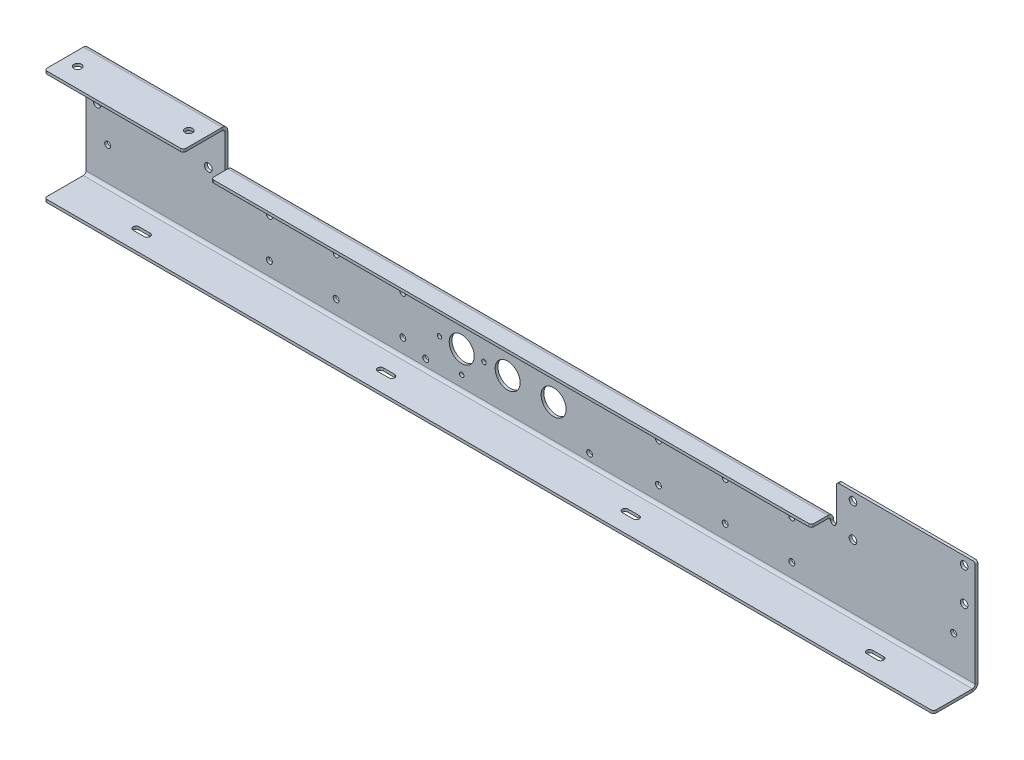
SolidWorks part; units mm, degrees
note: The reader was unsure of these and kept them because the rebuilt part matched: flange length of "Edge-Flange1", "Edge-Flange2", "Edge-Flange3".
ref_plane "Front Plane" through (0, 0, 0) normal (0, 0, 1) x (1, 0, 0)
ref_plane "Top Plane" through (0, 0, 0) normal (0, 1, 0) x (1, 0, 0)
ref_plane "Right Plane" through (0, 0, 0) normal (1, 0, 0) x (0, 0, -1)
sketch "Sketch1" plane through (0, 0, 0) normal (0, 0, 1) x (1, 0, 0)
  line L0 (-481.7491, 38.1) -> (-481.7491, 82.55)
  line L1 (-319.8241, 38.1) -> (-319.7987, 38.1)
  line L2 (-481.7491, 38.1) -> (-481.7491, -38.1)
  line L3 (-481.7491, -38.1) -> (534.2509, -38.1)
  line L4 (534.2509, 38.1) -> (534.2509, -38.1)
  line L5 (-481.7491, 38.1) -> (534.2509, -38.1) construction
  line L6 (-481.7491, -38.1) -> (534.2509, 38.1) construction
  line L7 (-93.6625, -30.1625) -> (93.6625, -30.1625) construction
  line L8 (-93.6625, -30.1625) -> (-93.6625, 30.1625) construction
  line L9 (-93.6625, 30.1625) -> (93.6625, 30.1625) construction
  line L10 (93.6625, -30.1625) -> (93.6625, 30.1625) construction
  line L11 (-93.6625, -30.1625) -> (93.6625, 30.1625) construction
  line L12 (-93.6625, 30.1625) -> (93.6625, -30.1625) construction
  line L13 (-77.9018, 0) -> (-52.5018, -25.4) construction
  line L14 (-77.9018, 0) -> (-52.5018, 25.4) construction
  line L15 (-52.5018, 25.4) -> (-27.1018, 0) construction
  line L16 (-52.5018, -25.4) -> (-27.1018, 0) construction
  line L17 (-77.9018, 0) -> (-27.1018, 0) construction
  line L18 (-52.5018, 25.4) -> (-52.5018, -25.4) construction
  line L19 (-481.7491, 82.55) -> (-322.9991, 82.55)
  line L20 (-322.9991, 82.55) -> (-322.9991, 41.275)
  line L21 (534.2509, 38.1) -> (534.2509, 82.55)
  line L22 (534.2509, 82.55) -> (375.5009, 82.55)
  line L23 (375.5009, 82.55) -> (375.5009, 41.275)
  line L24 (-316.6491, 41.5036) -> (369.1509, 41.5036)
  line L25 (369.1509, 41.5036) -> (369.1509, 41.2496)
  line L26 (-316.6491, 41.5036) -> (-316.6491, 41.2496)
  line L27 (372.3005, 38.1) -> (372.3259, 38.1)
  line L28 (-481.7491, 38.1) -> (534.2509, 38.1) construction
  line L29 (0, 0) -> (52.5018, 0) construction
  circle A0 centre (-457.073, 0) radius 3.3731
  circle A1 centre (0, 0) radius 14.2875
  circle A2 centre (-52.5018, 0) radius 14.2875
  circle A3 centre (52.5018, 0) radius 14.2875
  circle A4 centre (509.5748, 0) radius 3.3731
  circle A5 centre (-93.6625, 30.1625) radius 3.3734
  circle A6 centre (93.6625, 30.1625) radius 3.3734
  circle A7 centre (93.6625, -30.1625) radius 3.3734
  circle A8 centre (-93.6625, -30.1625) radius 3.3734
  circle A9 centre (-27.1018, 0) radius 2.5527
  circle A10 centre (-52.5018, 25.4) radius 2.5527
  circle A11 centre (-52.5018, -25.4) radius 2.5527
  circle A12 centre (-77.9018, 0) radius 2.5527
  arc A13 (375.5009, 41.275) -> (372.3259, 38.1) centre (372.3259, 41.275) cw
  arc A14 (-322.9991, 41.275) -> (-319.8241, 38.1) centre (-319.8241, 41.275) ccw
  arc A15 (369.1509, 41.2496) -> (372.3005, 38.1) centre (372.3005, 41.2496) ccw
  arc A16 (-316.6491, 41.2496) -> (-319.7987, 38.1) centre (-319.7987, 41.2496) cw
  point P0 (0, 0)
  point P49 (369.1509, 38.1)
  point P54 (26.2509, 0)
  dimension "D3" = 6.7462
  dimension "D9" = 6.7469
  dimension "D12" = 5.1054
  dimension "D15" = 28.575
  dimension "D18" = 3.175
  dimension "D21" = 3.1496
  dimension "D22" = 28.575
  dimension "D2" = 76.2
  dimension "D6" = 52.5018
  dimension "D7" = 52.5018
  dimension "D5" = 457.073
  dimension "D8" = 457.073
  dimension "D10" = 60.325
  dimension "D11" = 187.325
  dimension "D13" = 50.8
  dimension "D16" = 44.45
  dimension "D17" = 158.75
  dimension "D19" = 6.35
  dimension "D20" = 6.35
  dimension "D14" = 0.254
  dimension "D23" = 120.65
  dimension "D4" = 1016
base flange "Base-Flange1" sketch "Sketch1" thickness 3.175 reverse thickness direction no parameters "D1"=3.175
edge flange "Edge-Flange1" sketch "Sketch8" flange angle 90 flange length 50.8 flange position bend outside bend radius 3.175 thickness 3.175 relief rectangular parameters "D6"=10
sketch "Sketch8" plane through (0, -38.1, 0) normal (0, -1, 0) x (1, 0, 0)
  line L0 (-481.7491, 0) -> (534.2509, 0) construction
  line L1 (-481.7491, 0) -> (534.2509, 0)
  line L2 (-481.7491, 0) -> (-481.7491, 47.625)
  line L3 (-481.7491, 47.625) -> (534.2509, 47.625)
  line L4 (534.2509, 47.625) -> (534.2509, 0)
bend "EdgeBend1" bend radius 3.175 bend angle 90 parameters "D5"=1
edge flange "Edge-Flange2" sketch "Sketch17" flange angle 90 flange length 25.4 flange position bend outside bend radius 3.175 thickness 3.175 relief rectangular parameters "D6"=10, "D8"=1
bend "EdgeBend4" bend radius 3.175 bend angle 90 parameters "D5"=2
sketch "Sketch17" plane through (0, 41.5036, 0) normal (0, 1, 0) x (-1, 0, 0)
  line L0 (-369.1509, 0) -> (316.6491, 0) construction
  line L1 (-369.1509, 0) -> (316.6491, 0)
  line L2 (-369.1509, 0) -> (-369.1509, 22.225)
  line L3 (-369.1509, 22.225) -> (316.6491, 22.225)
  line L4 (316.6491, 22.225) -> (316.6491, 0)
edge flange "Edge-Flange3" sketch "Sketch22" flange angle 90 flange length 50.8 flange position material outside bend radius 3.175 thickness 3.175 relief rectangular parameters "D6"=10
sketch "Sketch22" plane through (0, 82.55, 0) normal (0, -1, 0) x (1, 0, 0)
  line L2 (-481.7491, 0) -> (-481.7491, 47.625)
  line L3 (-481.7491, 47.625) -> (-322.9991, 47.625)
  line L4 (-322.9991, 47.625) -> (-322.9991, 0)
  line L13 (-322.9991, 0) -> (-481.7491, 0) construction
  line L14 (-322.9991, 0) -> (-481.7491, 0)
bend "EdgeBend5" bend radius 3.175 bend angle 90 parameters "D5"=3
fillet "Fillet1" radius 3.175 8 edges at (369.1509, 46.2661, 22.225) (534.2509, -42.8625, 47.625) (-481.7491, -42.8625, 47.625) (-316.6491, 46.2661, 22.225) (534.2509, 82.55, -1.5875) (375.5009, 82.55, -1.5875) (-322.9991, 84.1375, 47.625) (-481.7491, 84.1375, 47.625)
sketch "Sketch23" plane through (0, 0, -3.175) normal (0, 0, -1) x (-1, 0, 0)
  line L6 (0, 0) -> (-52.5018, 0) construction
  line L24 (-324.7009, 22.225) -> (-172.3009, 22.225) construction
  line L25 (-324.7009, 22.225) -> (-324.7009, -22.225) construction
  line L26 (-324.7009, -22.225) -> (-172.3009, -22.225) construction
  line L27 (-172.3009, 22.225) -> (-172.3009, -22.225) construction
  line L28 (-324.7009, 22.225) -> (-172.3009, -22.225) construction
  line L29 (-324.7009, -22.225) -> (-172.3009, 22.225) construction
  line L30 (272.1991, -22.225) -> (119.7991, -22.225) construction
  line L31 (272.1991, -22.225) -> (272.1991, 22.225) construction
  line L32 (272.1991, 22.225) -> (119.7991, 22.225) construction
  line L33 (119.7991, -22.225) -> (119.7991, 22.225) construction
  line L34 (272.1991, -22.225) -> (119.7991, 22.225) construction
  line L35 (272.1991, 22.225) -> (119.7991, -22.225) construction
  point P0 (-248.5009, 0)
  point P5 (195.9991, 0)
  point P12 (-26.2509, 0)
  point P13 (-248.5009, 22.225)
  point P15 (-248.5009, -22.225)
  point P16 (195.9991, 22.225)
  point P17 (195.9991, -22.225)
  dimension "D1" = 146.05
  dimension "D2" = 146.05
  dimension "D3" = 152.4
  dimension "D4" = 152.4
  dimension "D5" = 44.45
hole_wizard "17/64 (0.26563) Diameter Hole1" positions "Sketch24" profile "Sketch25" hole size "17/64" standard "ANSI Inch" end condition through all
sketch "Sketch24" plane through (0, 0, -3.175) normal (0, 0, -1) x (-1, 0, 0)
  line L0 (-324.7009, -22.225) -> (-172.3009, -22.225) construction
  line L1 (272.1991, -22.225) -> (119.7991, -22.225) construction
  point P6 (-324.7009, -22.225)
  point P9 (-324.7009, 22.225)
  point P12 (-172.3009, 22.225)
  point P15 (-172.3009, -22.225)
  point P18 (119.7991, 22.225)
  point P21 (272.1991, 22.225)
  point P24 (272.1991, -22.225)
  point P27 (119.7991, -22.225)
  point P69 (-248.5009, 22.225)
  point P72 (-248.5009, -22.225)
  point P76 (195.9991, 22.225)
  point P79 (195.9991, -22.225)
sketch "Sketch25" plane through (324.7009, -22.225, -3.175) normal (1, 0, 0) x (0, 1, 0)
  line L0 (0, 0) -> (0, 50.8)
  line L1 (0, 50.8) -> (3.3735, 50.8)
  line L2 (3.3735, 50.8) -> (3.3735, 0)
  line L5 (3.3735, 0) -> (0, 0)
  line L11 (0, -6.35) -> (0, 107.95) construction
  dimension "Thru Hole Dia." = 6.747
  dimension "Thru Hole Depth" = 50.8
sketch "Sketch26" plane through (0, 0, -3.175) normal (0, 0, -1) x (-1, 0, 0)
  line L0 (-534.2509, -44.45) -> (481.7491, -44.45) construction
  line L1 (481.7491, 79.375) -> (481.7491, -38.1) construction
  line L2 (-534.2509, -38.1) -> (-534.2509, 79.375) construction
  line L3 (342.0491, 34.925) -> (469.0491, 34.925) construction
  line L4 (-521.5509, 73.025) -> (-394.5509, 73.025) construction
  line L5 (-521.5509, 73.025) -> (-521.5509, 34.925) construction
  line L6 (-521.5509, 34.925) -> (-394.5509, 34.925) construction
  line L7 (-394.5509, 73.025) -> (-394.5509, 34.925) construction
  line L8 (-521.5509, 73.025) -> (-394.5509, 34.925) construction
  line L9 (-521.5509, 34.925) -> (-394.5509, 73.025) construction
  line L10 (-531.0759, 82.55) -> (-378.6759, 82.55) construction
  line L11 (-32.6009, -44.45) -> (-32.6009, 47.8536) construction
  line L12 (316.6491, 47.8536) -> (-369.1509, 47.8536) construction
  line L13 (-19.9009, -44.45) -> (-19.9009, 47.8536) construction
  line L14 (399.1991, -12.7) -> (373.7991, -12.7) construction
  line L15 (-451.7009, -12.7) -> (-426.3009, -12.7) construction
  line L16 (386.4991, -12.7) -> (411.8991, -12.7) construction
  line L17 (-439.0009, -12.7) -> (-464.4009, -12.7) construction
  point P0 (-451.7009, -12.7)
  point P1 (-426.3009, -12.7)
  point P2 (373.7991, -12.7)
  point P3 (399.1991, -12.7)
  point P11 (-458.0509, 53.975)
  point P19 (-439.0009, -12.7)
  point P20 (-464.4009, -12.7)
  point P21 (386.4991, -12.7)
  point P22 (411.8991, -12.7)
  point P31 (386.4991, -12.7)
  point P34 (-439.0009, -12.7)
  point P37 (399.1991, -12.7)
  point P40 (-451.7009, -12.7)
  dimension "D1" = 25.4
  dimension "D2" = 31.75
  dimension "D3" = 25.4
  dimension "D4" = 38.1
  dimension "D5" = 419.1
  dimension "D6" = 419.1
  dimension "D7" = 127
  dimension "D8" = 9.525
  dimension "D9" = 12.7
  dimension "D10" = 12.7
  dimension "D11" = 25.4
  dimension "D12" = 25.4
  dimension "D13" = 419.1
  dimension "D14" = 419.1
  dimension "D15" = 501.65
  dimension "D16" = 501.65
hole_wizard "11/32 (0.34375) Diameter Hole1" positions "Sketch29" profile "Sketch30" hole size "11/32" standard "ANSI Inch" end condition through all
sketch "Sketch29" plane through (0, 0, -3.175) normal (0, 0, -1) x (-1, 0, 0)
  point P0 (-394.5509, 73.025)
  point P3 (-394.5509, 34.925)
  point P6 (-521.5509, 34.925)
  point P9 (-521.5509, 73.025)
  point P13 (342.0491, 34.925)
  point P16 (469.0491, 34.925)
sketch "Sketch30" plane through (394.5509, 73.025, -3.175) normal (1, 0, 0) x (0, 1, 0)
  line L0 (0, 0) -> (0, 50.8)
  line L1 (0, 50.8) -> (4.3656, 50.8)
  line L2 (4.3656, 50.8) -> (4.3656, 0)
  line L5 (4.3656, 0) -> (0, 0)
  line L11 (0, -6.35) -> (0, 107.95) construction
  dimension "Thru Hole Dia." = 8.7312
  dimension "Thru Hole Depth" = 50.8
sketch "Sketch31" plane through (0, 85.725, 0) normal (0, 1, 0) x (1, 0, 0)
  line L0 (-465.8741, -25.4) -> (-338.8741, -25.4) construction
  line L1 (-326.1741, -47.625) -> (-478.5741, -47.625) construction
  point P4 (-402.3741, -47.625)
  point P5 (-402.3741, -25.4)
  dimension "D1" = 127
  dimension "D2" = 22.225
hole_wizard "11/32 (0.34375) Diameter Hole2" positions "Sketch32" profile "Sketch33" hole size "11/32" standard "ANSI Inch" end condition up to next
sketch "Sketch32" plane through (0, 85.725, 0) normal (0, 1, 0) x (1, 0, 0)
  point P0 (-465.8741, -25.4)
  point P3 (-338.8741, -25.4)
sketch "Sketch33" plane through (-465.8741, 85.725, 25.4) normal (1, 0, 0) x (0, 0, 1)
  line L0 (0, 0) -> (0, 3.175)
  line L1 (0, 3.175) -> (4.3656, 3.175)
  line L2 (4.3656, 3.175) -> (4.3656, 0)
  line L5 (4.3656, 0) -> (0, 0)
  line L11 (0, -6.35) -> (0, 107.95) construction
  dimension "Thru Hole Dia." = 8.7312
  dimension "Thru Hole Depth" = 3.175
sketch "Sketch34" plane through (0, -41.275, 0) normal (0, 1, 0) x (1, 0, 0)
  line L0 (-326.1741, -47.625) -> (-478.5741, -47.625) construction
  line L1 (-399.1991, -25.4) -> (-386.4991, -25.4) construction
  line L2 (-399.1991, -22.0266) -> (-386.4991, -22.0266)
  line L3 (531.0759, -47.625) -> (-478.5741, -47.625) construction
  line L4 (-399.1991, -28.7734) -> (-386.4991, -28.7734)
  line L5 (-107.0991, -25.4) -> (-119.7991, -25.4) construction
  line L6 (-107.0991, -28.7734) -> (-119.7991, -28.7734)
  line L7 (-107.0991, -22.0266) -> (-119.7991, -22.0266)
  line L8 (-481.7491, -44.45) -> (-481.7491, -3.175) construction
  line L9 (159.6009, -25.4) -> (172.3009, -25.4) construction
  line L10 (159.6009, -22.0266) -> (172.3009, -22.0266)
  line L11 (159.6009, -28.7734) -> (172.3009, -28.7734)
  line L12 (439.0009, -25.4) -> (451.7009, -25.4) construction
  line L13 (439.0009, -22.0266) -> (451.7009, -22.0266)
  line L14 (439.0009, -28.7734) -> (451.7009, -28.7734)
  arc A0 (-399.1991, -22.0266) -> (-399.1991, -28.7734) centre (-399.1991, -25.4) ccw
  arc A1 (-386.4991, -28.7734) -> (-386.4991, -22.0266) centre (-386.4991, -25.4) ccw
  arc A2 (-107.0991, -28.7734) -> (-107.0991, -22.0266) centre (-107.0991, -25.4) ccw
  arc A3 (-119.7991, -22.0266) -> (-119.7991, -28.7734) centre (-119.7991, -25.4) ccw
  arc A4 (159.6009, -22.0266) -> (159.6009, -28.7734) centre (159.6009, -25.4) ccw
  arc A5 (172.3009, -28.7734) -> (172.3009, -22.0266) centre (172.3009, -25.4) ccw
  arc A6 (439.0009, -22.0266) -> (439.0009, -28.7734) centre (439.0009, -25.4) ccw
  arc A7 (451.7009, -28.7734) -> (451.7009, -22.0266) centre (451.7009, -25.4) ccw
  point P0 (19.9009, -47.625)
  point P3 (-399.1991, -25.4)
  point P6 (-119.7991, -25.4)
  point P9 (159.6009, -25.4)
  point P12 (439.0009, -25.4)
  point P19 (-386.4991, -25.4)
  point P20 (-107.0991, -25.4)
  point P23 (172.3009, -25.4)
  point P24 (451.7009, -25.4)
  point P25 (-392.8491, -25.4)
  point P30 (-113.4491, -25.4)
  point P37 (165.9509, -25.4)
  point P44 (445.3509, -25.4)
  dimension "D9" = 3.3734
  dimension "D2" = 279.4
  dimension "D3" = 279.4
  dimension "D4" = 279.4
  dimension "D5" = 501.65
  dimension "D1" = 139.7
  dimension "D6" = 22.225
  dimension "D8" = 12.7
sketch "Sketch41" plane through (0, 0, 0) normal (0, 0, 1) x (1, 0, 0)
  line L0 (506.4676, 1.3127) -> (507.664, 4.1447)
  line L1 (512.682, -1.3127) -> (514.8753, 3.8788)
  line L2 (509.0259, 12.7) -> (490.5248, 12.7)
  line L4 (490.5248, 6.35) -> (506.2017, 6.35)
  circle A0 centre (509.5748, 0) radius 3.3731 construction
  circle A1 centre (-457.073, 0) radius 3.3731 construction
  circle A2 centre (509.5748, 0) radius 3.3731
  circle A3 centre (-457.073, 0) radius 3.3731
  arc A4 (490.5248, 12.7) -> (490.5248, 6.35) centre (490.5248, 9.525) ccw
  arc A5 (507.664, 4.1447) -> (506.2017, 6.35) centre (506.2017, 4.7625) ccw
  arc A6 (514.8753, 3.8788) -> (509.0259, 12.7) centre (509.0259, 6.35) ccw
  arc A7 (-457.073, 0) -> (-451.3825, 71.8997) centre (0, 0) cw construction
  arc A8 (-457.073, 0) -> (-450.2671, 25.4) centre (-406.273, 0) cw construction
  arc A9 (-452.4778, 26.6763) -> (-459.6257, 0) centre (-406.273, 0) ccw
  arc A10 (-448.0564, 24.1236) -> (-454.5203, 0) centre (-406.273, 0) ccw
  arc A11 (-448.0564, 24.1236) -> (-452.4778, 26.6763) centre (-450.2671, 25.4) ccw
  arc A12 (-459.6257, 0) -> (-454.5203, 0) centre (-457.073, 0) ccw
  point P17 (506.2017, 0)
  point P18 (507.7892, 4.7625)
  point P24 (-455.342, 13.148)
  dimension "D1" = 6.35
  dimension "D4" = 3.175
  dimension "D6" = 1.5875
  dimension "D7" = 2.5527
  dimension "D8" = 50.8
  dimension "D2" = 19.05
  dimension "D3" = 9.525
  dimension "D5" = 1.5875
  dimension "D9" = 25.4
extrude "Cut-Extrude1" [suppressed] cut sketch "Sketch41" against normal through all contours A10 A11 A9 A3 | L1 A6 L2 A4 L4 A5 L0 A2
extrude "Cut-Extrude2" cut sketch "Sketch34" against normal through all normal cut yes
ref_plane "Plane1" through (26.2509, 0, 0) normal (1, 0, 0) x (0, 0, -1)
sketch "Bend-Lines1" [suppressed] plane through (0, 0, 0) normal (0, 1, 0) x (1, 0, 0)
sketch "Bounding-Box1" [suppressed] plane through (0, 0, 0) normal (0, 1, 0) x (1, 0, 0)
sheet metal parameters "Sheet-Metal2" thickness 3.175 parameters "D1"=3.175
flat pattern "Flat-Pattern2" [suppressed]
sketch "Bend-Lines2" plane through (0, 0, 0) normal (0, 1, 0) x (1, 0, 0)
sketch3d "Bounding-Box2" [suppressed]
  line L0 (-155.575, -79.375, 0) -> (881.38, -79.375, 0) construction
  line L1 (-155.575, 47.625, 0) -> (881.38, 47.625, 0) construction
  line L2 (-155.575, -79.375, 0) -> (-155.575, 47.625, 0) construction
  line L3 (881.38, -79.375, 0) -> (881.38, 47.625, 0) construction
sheet metal parameters "Sheet-Metal3" thickness 3.175 parameters "D1"=3.175
flat pattern "Flat-Pattern2"
sketch "Bend-Lines2" plane through (0, 0, 0) normal (0, 0, 1) x (1, 0, 0)
  line L0 (-492.2266, -41.8405) -> (544.7284, -41.8405) construction
  line L1 (-492.2266, -41.8405) -> (544.7284, -41.8405) construction
sketch3d "Bounding-Box2" [suppressed]
  line L0 (-155.5748, 47.6252, 0) -> (881.38, 47.6239, 0) construction
  line L1 (-155.575, -131.3046, 0) -> (881.3798, -131.3059, 0) construction
  line L2 (-155.5748, 47.6252, 0) -> (-155.575, -131.3046, 0) construction
  line L3 (881.38, 47.6239, 0) -> (881.3798, -131.3059, 0) construction
bend of the flat pattern "Flatten-<EdgeBend1>1"
sheet metal parameters "Sheet-Metal4" thickness 3.175 parameters "D1"=3.175
flat pattern "Flat-Pattern2"
sketch "Bend-Lines2" plane through (0, 0, 0) normal (0, 0, 1) x (1, 0, 0)
  line L0 (-485.775, -41.8405) -> (538.2768, -41.8405) construction
  line L1 (-485.775, -41.8405) -> (538.2768, -41.8405) construction
  line L2 (373.1768, 45.2441) -> (-320.675, 45.2441) construction
  line L3 (373.1768, 45.2441) -> (-320.675, 45.2441) construction
sketch3d "Bounding-Box2" [suppressed]
  line L0 (-161.9248, 41.2752, 0) -> (862.1268, 41.2739, 0) construction
  line L1 (-161.925, -131.3046, 0) -> (862.1266, -131.3059, 0) construction
  line L2 (-161.9248, 41.2752, 0) -> (-161.925, -131.3046, 0) construction
  line L3 (862.1268, 41.2739, 0) -> (862.1266, -131.3059, 0) construction
bend of the flat pattern "Flatten-<EdgeBend1>1"
bend of the flat pattern "Flatten-<EdgeBend4>1"
sheet metal parameters "Sheet-Metal5" thickness 3.175 parameters "D1"=3.175
flat pattern "Flat-Pattern2"
sketch "Bend-Lines2" plane through (0, 0, 0) normal (0, 0, 1) x (1, 0, 0)
  line L0 (-485.775, -41.8405) -> (538.2768, -41.8405) construction
  line L1 (-485.775, -41.8405) -> (538.2768, -41.8405) construction
  line L2 (373.1768, 45.2441) -> (-320.675, 45.2441) construction
  line L3 (373.1768, 45.2441) -> (-320.675, 45.2441) construction
  line L4 (-327.025, 79.9405) -> (-485.775, 79.9405) construction
  line L5 (-327.025, 79.9405) -> (-485.775, 79.9405) construction
sketch3d "Bounding-Box2" [suppressed]
  line L0 (-161.9247, 86.8561, 0) -> (862.1269, 86.8548, 0) construction
  line L1 (-161.925, -131.3046, 0) -> (862.1266, -131.3059, 0) construction
  line L2 (-161.9247, 86.8561, 0) -> (-161.925, -131.3046, 0) construction
  line L3 (862.1269, 86.8548, 0) -> (862.1266, -131.3059, 0) construction
bend of the flat pattern "Flatten-<EdgeBend1>1"
bend of the flat pattern "Flatten-<EdgeBend4>1"
bend of the flat pattern "Flatten-<EdgeBend5>1"
sheet metal parameters "Sheet-Metal7" thickness 3.175 parameters "D1"=3.175
flat pattern "Flat-Pattern2" [suppressed]
sketch "Bend-Lines2" plane through (0, 0, 0) normal (0, 0, 1) x (1, 0, 0)
  line L0 (-485.775, -41.8405) -> (538.2768, -41.8405) construction
  line L1 (-485.775, -41.8405) -> (538.2768, -41.8405) construction
  line L2 (373.1768, 45.2441) -> (-320.675, 45.2441) construction
  line L3 (373.1768, 45.2441) -> (-320.675, 45.2441) construction
  line L4 (-327.025, 83.1155) -> (-485.775, 83.1155) construction
  line L5 (-327.025, 83.1155) -> (-485.775, 83.1155) construction
sketch3d "Bounding-Box2" [suppressed]
  line L0 (-161.9247, 90.0311, 0) -> (862.1269, 90.0298, 0) construction
  line L1 (-161.925, -131.3046, 0) -> (862.1266, -131.3059, 0) construction
  line L2 (-161.9247, 90.0311, 0) -> (-161.925, -131.3046, 0) construction
  line L3 (862.1269, 90.0298, 0) -> (862.1266, -131.3059, 0) construction
bend of the flat pattern "Flatten-<EdgeBend1>1"
bend of the flat pattern "Flatten-<EdgeBend4>1"
bend of the flat pattern "Flatten-<EdgeBend5>1"
sheet metal parameters "Sheet-Metal9" thickness 3.175 parameters "D1"=3.175
flat pattern "Flat-Pattern2"
sketch "Bend-Lines2" plane through (0, 0, 0) normal (0, 0, 1) x (1, 0, 0)
  line L0 (-485.775, -41.8405) -> (538.2768, -41.8405) construction
  line L1 (-485.775, -41.8405) -> (538.2768, -41.8405) construction
  line L2 (373.1768, 45.2441) -> (-320.675, 45.2441) construction
  line L3 (373.1768, 45.2441) -> (-320.675, 45.2441) construction
  line L4 (-327.025, 92.6405) -> (-485.775, 92.6405) construction
  line L5 (-327.025, 92.6405) -> (-485.775, 92.6405) construction
sketch3d "Bounding-Box2" [suppressed]
  line L0 (-161.9247, 99.5561, 0) -> (862.1269, 99.5548, 0) construction
  line L1 (-161.925, -131.3046, 0) -> (862.1266, -131.3059, 0) construction
  line L2 (-161.9247, 99.5561, 0) -> (-161.925, -131.3046, 0) construction
  line L3 (862.1269, 99.5548, 0) -> (862.1266, -131.3059, 0) construction
bend of the flat pattern "Flatten-<EdgeBend1>1"
bend of the flat pattern "Flatten-<EdgeBend4>1"
bend of the flat pattern "Flatten-<EdgeBend5>1"
sheet metal parameters "Sheet-Metal10" thickness 3.175 parameters "D1"=3.175
flat pattern "Flat-Pattern2" [suppressed]
sketch "Bend-Lines2" plane through (0, 0, 0) normal (0, 0, 1) x (1, 0, 0)
  line L0 (-481.7491, -41.8405) -> (534.2509, -41.8405) construction
  line L1 (-481.7491, -41.8405) -> (534.2509, -41.8405) construction
  line L2 (369.1509, 45.2441) -> (-316.6491, 45.2441) construction
  line L3 (369.1509, 45.2441) -> (-316.6491, 45.2441) construction
  line L4 (-322.9991, 83.1155) -> (-481.7491, 83.1155) construction
  line L5 (-322.9991, 83.1155) -> (-481.7491, 83.1155) construction
sketch3d "Bounding-Box2" [suppressed]
  line L0 (-161.9247, 90.0311, 0) -> (854.0751, 90.0298, 0) construction
  line L1 (-161.925, -131.3046, 0) -> (854.0748, -131.3059, 0) construction
  line L2 (-161.9247, 90.0311, 0) -> (-161.925, -131.3046, 0) construction
  line L3 (854.0751, 90.0298, 0) -> (854.0748, -131.3059, 0) construction
bend of the flat pattern "Flatten-<EdgeBend1>1"
bend of the flat pattern "Flatten-<EdgeBend4>1"
bend of the flat pattern "Flatten-<EdgeBend5>1"
sketch "Sketch31-1" plane through (0, 83.6809, -3.175) normal (0, 0, -1) x (1, 0, 0)
  line L0 (-465.8741, -25.4) -> (-338.8741, -25.4) construction
  line L1 (-326.1741, -47.625) -> (-478.5741, -47.625) construction
  point P4 (-402.3741, -47.625)
  point P5 (-402.3741, -25.4)
  dimension "D1" = 127
  dimension "D2" = 22.225
sketch "Sketch34-2" plane through (0, -42.4059, 0) normal (0, 0, 1) x (1, 0, 0)
  line L0 (-326.1741, 173.7118) -> (-478.5741, 173.7118) construction
  line L8 (-481.7491, 170.5368) -> (-481.7491, -44.45) construction
  point P0 (19.9009, -47.625)
  point P3 (-399.1991, -25.4)
  point P6 (-119.7991, -25.4)
  point P9 (159.6009, -25.4)
  point P12 (439.0009, -25.4)
  point P19 (-386.4991, -25.4)
  point P20 (-107.0991, -25.4)
  point P23 (172.3009, -25.4)
  point P24 (451.7009, -25.4)
  dimension "D1" = 139.7
  dimension "D2" = 279.4
  dimension "D3" = 279.4
  dimension "D4" = 279.4
  dimension "D5" = 501.65
  dimension "D6" = 199.1118
  dimension "D7" = 2
  dimension "D8" = 12.7
sheet metal parameters "Sheet-Metal14" thickness 3.175 parameters "D1"=3.175
flat pattern "Flat-Pattern2" [suppressed]
sketch "Bend-Lines2" plane through (0, 0, 0) normal (0, 0, 1) x (1, 0, 0)
  line L0 (-481.7491, -41.8405) -> (534.2509, -41.8405) construction
  line L1 (-481.7491, -41.8405) -> (534.2509, -41.8405) construction
  line L2 (369.1509, 45.2441) -> (-316.6491, 45.2441) construction
  line L3 (369.1509, 45.2441) -> (-316.6491, 45.2441) construction
  line L4 (-322.9991, 83.1155) -> (-481.7491, 83.1155) construction
  line L5 (-322.9991, 83.1155) -> (-481.7491, 83.1155) construction
sketch3d "Bounding-Box2" [suppressed]
  line L0 (-161.9247, 90.0311, 0) -> (854.0751, 90.0298, 0) construction
  line L1 (-161.925, -131.3046, 0) -> (854.0748, -131.3059, 0) construction
  line L2 (-161.9247, 90.0311, 0) -> (-161.925, -131.3046, 0) construction
  line L3 (854.0751, 90.0298, 0) -> (854.0748, -131.3059, 0) construction
bend of the flat pattern "Flatten-<EdgeBend1>1"
bend of the flat pattern "Flatten-<EdgeBend4>1"
bend of the flat pattern "Flatten-<EdgeBend5>1"
sketch "Sketch31-1" plane through (0, 83.6809, -3.175) normal (0, 0, -1) x (1, 0, 0)
  line L0 (-465.8741, -25.4) -> (-338.8741, -25.4) construction
  line L1 (-326.1741, -47.625) -> (-478.5741, -47.625) construction
  point P4 (-402.3741, -47.625)
  point P5 (-402.3741, -25.4)
  dimension "D1" = 127
  dimension "D2" = 22.225
sketch "Sketch34-2" plane through (0, -42.4059, 0) normal (0, 0, 1) x (1, 0, 0)
  line L0 (-326.1741, 173.7118) -> (-478.5741, 173.7118) construction
  line L1 (-399.1991, -25.4) -> (-386.4991, -25.4) construction
  line L2 (-399.1991, -22.0266) -> (-386.4991, -22.0266)
  line L4 (-399.1991, -28.7734) -> (-386.4991, -28.7734)
  line L5 (-107.0991, -25.4) -> (-119.7991, -25.4) construction
  line L6 (-107.0991, -28.7734) -> (-119.7991, -28.7734)
  line L7 (-107.0991, -22.0266) -> (-119.7991, -22.0266)
  line L8 (-481.7491, 170.5368) -> (-481.7491, -44.45) construction
  line L9 (159.6009, -25.4) -> (172.3009, -25.4) construction
  line L10 (159.6009, -22.0266) -> (172.3009, -22.0266)
  line L11 (159.6009, -28.7734) -> (172.3009, -28.7734)
  line L12 (439.0009, -25.4) -> (451.7009, -25.4) construction
  line L13 (439.0009, -22.0266) -> (451.7009, -22.0266)
  line L14 (439.0009, -28.7734) -> (451.7009, -28.7734)
  arc A0 (-399.1991, -22.0266) -> (-399.1991, -28.7734) centre (-399.1991, -25.4) ccw
  arc A1 (-386.4991, -28.7734) -> (-386.4991, -22.0266) centre (-386.4991, -25.4) ccw
  arc A2 (-107.0991, -28.7734) -> (-107.0991, -22.0266) centre (-107.0991, -25.4) ccw
  arc A3 (-119.7991, -22.0266) -> (-119.7991, -28.7734) centre (-119.7991, -25.4) ccw
  arc A4 (159.6009, -22.0266) -> (159.6009, -28.7734) centre (159.6009, -25.4) ccw
  arc A5 (172.3009, -28.7734) -> (172.3009, -22.0266) centre (172.3009, -25.4) ccw
  arc A6 (439.0009, -22.0266) -> (439.0009, -28.7734) centre (439.0009, -25.4) ccw
  arc A7 (451.7009, -28.7734) -> (451.7009, -22.0266) centre (451.7009, -25.4) ccw
  point P0 (19.9009, -47.625)
  point P3 (-399.1991, -25.4)
  point P6 (-119.7991, -25.4)
  point P9 (159.6009, -25.4)
  point P12 (439.0009, -25.4)
  point P19 (-386.4991, -25.4)
  point P20 (-107.0991, -25.4)
  point P23 (172.3009, -25.4)
  point P24 (451.7009, -25.4)
  point P25 (-392.8491, -25.4)
  point P30 (-113.4491, -25.4)
  point P37 (165.9509, -25.4)
  point P44 (445.3509, -25.4)
  dimension "D9" = 3.3734
  dimension "D1" = 139.7
  dimension "D2" = 279.4
  dimension "D3" = 279.4
  dimension "D4" = 279.4
  dimension "D5" = 501.65
  dimension "D6" = 199.1118
  dimension "D7" = 2
  dimension "D8" = 12.7
equation "\"D7@Sketch1\"=\"D6@Sketch1\""
equation "\"D8@Sketch1\"=\"D5@Sketch1\""
equation "\"D4@Sketch34\"=\"D3@Sketch34\""
equation "\"D2@Sketch34\"=\"D3@Sketch34\""
